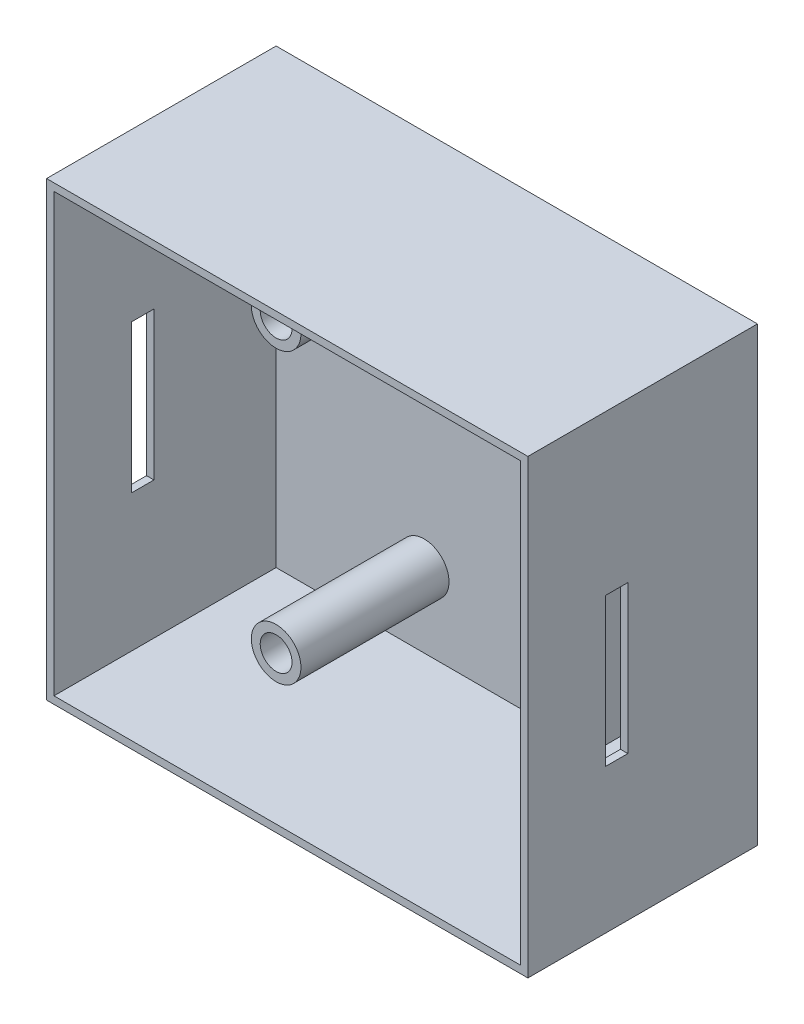
SolidWorks part; units mm, degrees
ref_plane "Alzado" through (0, 0, 0) normal (0, 0, 1) x (1, 0, 0)
ref_plane "Planta" through (0, 0, 0) normal (0, 1, 0) x (1, 0, 0)
ref_plane "Vista lateral" through (0, 0, 0) normal (1, 0, 0) x (0, 0, -1)
sketch "Croquis1" plane through (0, 0, 0) normal (0, 0, 1) x (1, 0, 0)
  line L0 (-31.5, 29.5) -> (-11.5, 29.5) construction
  line L1 (32.5, -30.5) -> (-32.5, -30.5)
  line L2 (32.5, -30.5) -> (32.5, 30.5)
  line L3 (32.5, 30.5) -> (-32.5, 30.5)
  line L4 (-32.5, -30.5) -> (-32.5, 30.5)
  line L5 (32.5, -30.5) -> (-32.5, 30.5) construction
  line L6 (32.5, 30.5) -> (-32.5, -30.5) construction
  line L7 (-31.5, -29.5) -> (31.5, -29.5)
  line L8 (-31.5, -29.5) -> (-31.5, 29.5)
  line L9 (-31.5, 29.5) -> (31.5, 29.5)
  line L10 (31.5, -29.5) -> (31.5, 29.5)
  line L11 (-31.5, -29.5) -> (31.5, 29.5) construction
  line L12 (-31.5, 29.5) -> (31.5, -29.5) construction
  line L13 (-11.5, 29.5) -> (-11.5, 19.5) construction
  line L14 (-11.5, -29.5) -> (-11.5, -19.5) construction
  line L15 (-31.5, 0) -> (31.5, 0) construction
  line L16 (31.5, 29.5) -> (31.5, 24.5) construction
  line L17 (31.5, 24.5) -> (17.5, 24.5)
  line L18 (17.5, 24.5) -> (17.5, -23.5)
  line L19 (17.5, -23.5) -> (31.5, -23.5)
  line L20 (31.5, -23.5) -> (31.5, -29.5)
  line L21 (31.5, -23.5) -> (31.5, -22.5)
  line L22 (17.5, -22.5) -> (18.5, -22.5) construction
  line L23 (31.5, -22.5) -> (18.5, -22.5)
  line L24 (31.5, 24.5) -> (31.5, 23.5) construction
  line L25 (17.5, 23.5) -> (18.5, 23.5) construction
  line L26 (31.5, 23.5) -> (18.5, 23.5)
  line L27 (18.5, 23.5) -> (18.5, -22.5)
  circle A0 centre (-11.5, -19.5) radius 2.15
  circle A1 centre (-11.5, -19.5) radius 3.35
  circle A2 centre (-11.5, 19.5) radius 2.15
  circle A3 centre (-11.5, 19.5) radius 3.35
  point P0 (0, 0)
  point P6 (0, 0)
  dimension "D8" = 4.3
  dimension "D9" = 6.7
  dimension "D1" = 61
  dimension "D2" = 65
  dimension "D3" = 63
  dimension "D4" = 59
  dimension "D5" = 20
  dimension "D6" = 10
  dimension "D7" = 10
  dimension "D10" = 5
  dimension "D11" = 14
  dimension "D12" = 48
  dimension "D13" = 1
  dimension "D14" = 1
  dimension "D15" = 1
  dimension "D16" = 1
extrude "Saliente-Extruir1" add sketch "Croquis1" along normal blind 30 contours L4 L1 L2 L3 L10 L7 L8 L9 region at (0, -29.6086, 0)
extrude "Saliente-Extruir2" add sketch "Croquis1<7>" along normal blind 20 separate body contours A3 A2 | A1 A0 region at (-14.7552, -19.5, 0) region at (-14.7552, 19.5, 0)
sketch "Croquis1<7>" plane through (0, 0, 0) normal (0, 0, 1) x (1, 0, 0) same geometry as "Croquis1"
extrude "Saliente-Extruir4" add sketch "Croquis1<9>" along normal blind 10 contours L27 L26 L10 L17 L18 L19 L23 region at (24.5, -23, 0)
sketch "Croquis1<9>" plane through (0, 0, 0) normal (0, 0, 1) x (1, 0, 0) same geometry as "Croquis1"
sketch "Croquis2" plane through (0, 0, 0) normal (0, 0, -1) x (-1, 0, 0)
  line L1 (-32.5, 30.5) -> (32.5, 30.5)
  line L2 (-32.5, 30.5) -> (-32.5, -30.5)
  line L3 (-32.5, -30.5) -> (32.5, -30.5)
  line L4 (32.5, 30.5) -> (32.5, -30.5)
extrude "Saliente-Extruir5" add sketch "Croquis2" along normal blind 1
sketch "Croquis3" plane through (0, 0, 0) normal (1, 0, 0) x (0, 0, -1)
  line L0 (1, -30.5) -> (1, 30.5) construction
  line L1 (-19.5, 9) -> (-16.5, 9)
  line L2 (-19.5, 9) -> (-19.5, -11)
  line L3 (-19.5, -11) -> (-16.5, -11)
  line L4 (-16.5, 9) -> (-16.5, -11)
  line L5 (1, -30.5) -> (-30, -30.5) construction
  dimension "D1" = 17.5
  dimension "D2" = 20
  dimension "D3" = 3
  dimension "D4" = 19.5
extrude "Cortar-Extruir1" cut sketch "Croquis3" against normal through all both and the other way through all
sketch "Croquis5" plane through (0, 0, 20) normal (0, 0, 1) x (1, 0, 0)
  circle A0 centre (-11.5, -19.5) radius 2.15
  circle A1 centre (-11.5, 19.5) radius 2.15
  dimension "D1" = 4.3
  dimension "D2" = 4.3
extrude "Cortar-Extruir2" cut sketch "Croquis5" against normal blind 40
